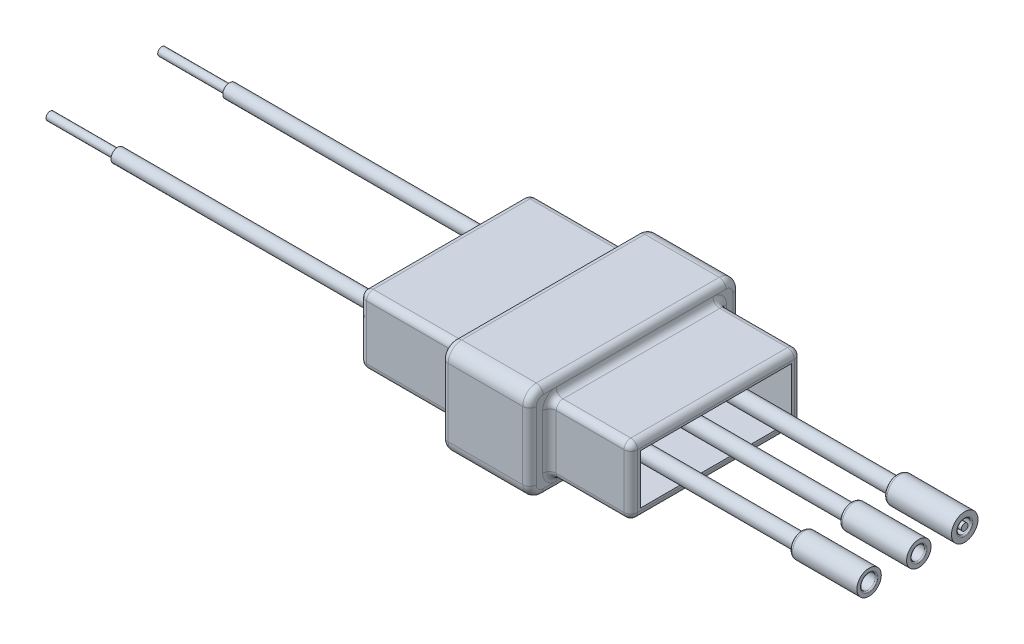
SolidWorks part; units mm, degrees
material "6061-T6 (SS)"
ref_plane "Front Plane" through (0, 0, 0) normal (0, 0, 1) x (1, 0, 0)
ref_plane "Top Plane" through (0, 0, 0) normal (0, 1, 0) x (1, 0, 0)
ref_plane "Right Plane" through (0, 0, 0) normal (1, 0, 0) x (0, 0, -1)
sketch "Sketch1" plane through (0, 0, 0) normal (0, 1, 0) x (1, 0, 0)
  line L1 (0, 0) -> (40, 0)
  line L2 (0, 0) -> (0, 31)
  line L3 (0, 31) -> (40, 31)
  line L4 (40, 0) -> (40, 31)
  dimension "D1" = 40
  dimension "D2" = 31
extrude "Boss-Extrude1" add sketch "Sketch1" along normal blind 14
sketch "Sketch5" plane through (0, 0, 0) normal (0, 0, 1) x (1, 0, 0)
  line L0 (0, 7) -> (40, 7) construction
  line L1 (0, 14) -> (15, 14)
  line L2 (0, 14) -> (0, 12)
  line L3 (0, 12) -> (15, 12)
  line L4 (15, 14) -> (15, 12)
  line L5 (0, 14) -> (0, 0) construction
  line L6 (40, 14) -> (40, 0) construction
  line L7 (20, 14) -> (20, 0) construction
  line L8 (0, 14) -> (40, 14) construction
  line L9 (0, 0) -> (40, 0) construction
  line L10 (15, 0) -> (15, 2)
  line L11 (0, 2) -> (15, 2)
  line L12 (0, 0) -> (0, 2)
  line L13 (0, 0) -> (15, 0)
  line L14 (28, 0) -> (28, 2)
  line L15 (40, 14) -> (28, 14)
  line L16 (40, 14) -> (40, 12)
  line L17 (40, 12) -> (28, 12)
  line L18 (28, 14) -> (28, 12)
  line L19 (40, 2) -> (28, 2)
  line L20 (40, 0) -> (40, 2)
  line L21 (40, 0) -> (28, 0)
  dimension "D1" = 2
  dimension "D2" = 15
  dimension "D3" = 2
  dimension "D4" = 12
extrude "Cut-Extrude4" cut sketch "Sketch5" against normal up to next
sketch "Sketch6" plane through (0, 0, 0) normal (0, 1, 0) x (1, 0, 0)
  line L0 (40, 28.0574) -> (28, 28.0574)
  line L1 (0, 31) -> (0, 0) construction
  line L2 (15, 31) -> (15, 0) construction
  line L3 (15, 31) -> (15, 0) construction
  line L4 (0, 15.5) -> (40, 15.5) construction
  line L5 (40, 31) -> (40, 0) construction
  line L6 (0, 2.9513) -> (15, 2.9513)
  line L7 (21.5, 31) -> (21.5, 0) construction
  line L8 (28, 31) -> (15, 31) construction
  line L9 (15, 0) -> (28, 0) construction
  line L10 (28, 31) -> (28, 0) construction
  line L12 (0, 2.9513) -> (0, 0)
  line L13 (0, 0) -> (15, 0)
  line L14 (15, 31) -> (0, 31)
  line L15 (0, 31) -> (0, 28.0487)
  line L16 (28, 31) -> (40, 31)
  line L17 (40, 31) -> (40, 28.0574)
  line L18 (28, 0) -> (40, 0)
  line L19 (40, 0) -> (40, 2.9426)
  line L25 (15, 0) -> (28, 0) construction
  line L26 (28, 31) -> (28, 0) construction
  line L31 (15, 31) -> (15, 0) construction
  line L32 (15, 2.9513) -> (15, 0)
  line L33 (0, 28.0487) -> (15, 28.0487)
  line L34 (15, 28.0487) -> (15, 31)
  line L35 (28, 28.0574) -> (28, 31)
  line L36 (40, 2.9426) -> (28, 2.9426)
  line L37 (28, 2.9426) -> (28, 0)
extrude "Cut-Extrude5" cut sketch "Sketch6" along normal up to next
fillet "Fillet4" radius 1 32 edges at (15, 12, -15.5) (15, 14, -15.5) (28, 14, -15.5) (28, 12, -15.5) (28, 0, -15.5) (28, 7, 0) (28, 7, -31) (28, 7, -2.9426) (28, 2, -15.5) (28, 7, -28.0574) (15, 7, -28.0487) (15, 2, -15.5) (15, 7, -2.9513) (15, 7, -31) (15, 7, 0) (15, 0, -15.5) (40, 2, -15.5) (7.5, 12, -2.9513) (7.5, 12, -28.0487) (0, 7, -28.0487) (0, 12, -15.5) (0, 7, -2.9513) (7.5, 2, -28.0487) (0, 2, -15.5) (7.5, 2, -2.9513) (40, 12, -15.5) (34, 2, -2.9426) (34, 12, -2.9426) (40, 7, -2.9426) (34, 2, -28.0574) (40, 7, -28.0574) (34, 12, -28.0574)
sketch "Sketch7" plane through (40, 0, 0) normal (1, 0, 0) x (0, 0, -1)
  line L0 (15.5, 11) -> (15.5, 3) construction
  line L1 (27.0574, 11) -> (3.9426, 11) construction
  line L2 (3.9426, 3) -> (27.0574, 3) construction
  line L4 (4.3871, 3.3393) -> (26.6129, 3.3393)
  line L5 (4.3871, 3.3393) -> (4.3871, 10.6607)
  line L6 (4.3871, 10.6607) -> (26.6129, 10.6607)
  line L7 (26.6129, 3.3393) -> (26.6129, 10.6607)
  line L8 (4.3871, 3.3393) -> (26.6129, 10.6607) construction
  line L9 (4.3871, 10.6607) -> (26.6129, 3.3393) construction
  point P6 (15.5, 7)
extrude "Cut-Extrude6" cut sketch "Sketch7" against normal blind 10
sketch "Sketch8" plane through (30, 0, 0) normal (1, 0, 0) x (0, 0, -1)
  line L0 (4.3871, 7) -> (26.6129, 7) construction
  line L1 (4.3871, 10.6607) -> (4.3871, 3.3393) construction
  line L2 (26.6129, 3.3393) -> (26.6129, 10.6607) construction
  circle A0 centre (15.5, 7) radius 1.1
  circle A1 centre (8.095, 7) radius 1.1
  circle A2 centre (22.205, 7) radius 1.1
  dimension "D1" = 2.2
extrude "Boss-Extrude2" add sketch "Sketch8" along normal blind 30
sketch "Sketch9" plane through (60, 0, 0) normal (1, 0, 0) x (0, 0, -1)
  circle A0 centre (8.095, 7) radius 1.8
  circle A1 centre (8.095, 7) radius 1.1
  circle A2 centre (15.433, 7) radius 1.8
  circle A3 centre (22.205, 7) radius 1.9575
  circle A4 centre (22.205, 7) radius 0.9922
  circle A5 centre (15.433, 7) radius 1.0166
extrude "Boss-Extrude3" add sketch "Sketch9" along normal blind 10
sketch "Sketch11" plane through (60, 0, 0) normal (1, 0, 0) x (0, 0, -1)
  circle A0 centre (22.205, 7) radius 0.5
  dimension "D1" = 1
fillet "Fillet5" radius 0.5 1 edges at (60, 7, -9.895)
fillet "Fillet6" radius 0.5 2 edges at (60, 7, -24.1626) (60, 7, -17.233)
fillet "Fillet7" radius 0.2 1 edges at (70, 7, -9.195)
fillet "Fillet8" radius 0.2 2 edges at (70, 7, -23.1973) (70, 7, -16.4497)
extrude "Boss-Extrude5" add sketch "Sketch11" along normal blind 10
sketch "Sketch12" plane through (0, 0, 0) normal (-1, 0, 0) x (0, 0, 1)
  line L0 (-27.0487, 7) -> (-3.9513, 7) construction
  line L1 (-27.0487, 11) -> (-27.0487, 3) construction
  line L2 (-3.9513, 3) -> (-3.9513, 11) construction
  circle A0 centre (-23.7487, 7) radius 1
  circle A1 centre (-7.2513, 7) radius 1
  dimension "D1" = 2
extrude "Boss-Extrude6" add sketch "Sketch12" along normal blind 40 and the other way blind 12 separate body
sketch "Sketch13" plane through (-40, 0, 0) normal (-1, 0, 0) x (0, 0, 1)
  circle A0 centre (-23.7487, 7) radius 0.6
  circle A1 centre (-7.2693, 7) radius 0.6
extrude "Boss-Extrude7" add sketch "Sketch13" along normal blind 10
sketch "Sketch14" plane through (0, 0, 0) normal (-1, 0, 0) x (0, 0, 1)
  line L1 (-26.2509, 10.2986) -> (-4.6895, 10.2986)
  line L2 (-26.2509, 10.2986) -> (-26.2509, 3.7551)
  line L3 (-26.2509, 3.7551) -> (-4.6895, 3.7551)
  line L4 (-4.6895, 10.2986) -> (-4.6895, 3.7551)
extrude "Cut-Extrude8" cut sketch "Sketch14" against normal blind 12
ref_plane "Plane1" through (0, 23.22, 0) normal (0, 1, 0) x (1, 0, 0)
fillet "Fillet10" radius 2 12 edges at (27.7071, 13.7071, -0.2929) (15.2929, 13.7071, -0.2929) (27.7071, 0.2929, -0.2929) (15.2929, 0.2929, -0.2929) (15.2929, 0.2929, -30.7071) (27.7071, 0.2929, -30.7071) (15.2929, 13.7071, -30.7071) (27.7071, 13.7071, -30.7071) (21.5, 14, -31) (21.5, 0, -31) (21.5, 0, 0) (21.5, 14, 0)
